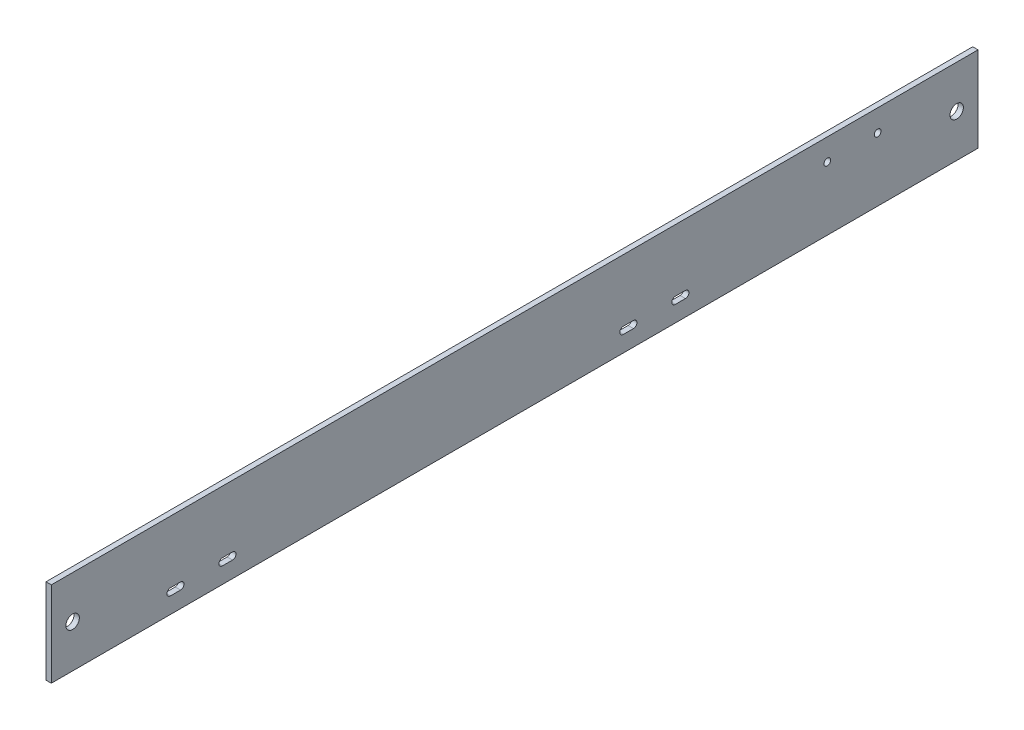
SolidWorks part; units mm, degrees
ref_plane "Front Plane" through (0, 0, 0) normal (0, 0, 1) x (1, 0, 0)
ref_plane "Top Plane" through (0, 0, 0) normal (0, 1, 0) x (1, 0, 0)
ref_plane "Right Plane" through (0, 0, 0) normal (1, 0, 0) x (0, 0, -1)
sketch "Sketch1" plane through (0, 0, 0) normal (1, 0, 0) x (0, 0, -1)
  line L0 (71.025, 11.7) -> (77.025, 11.7) construction
  line L1 (0, 0) -> (552.45, 0)
  line L2 (0, 0) -> (0, 50.8)
  line L3 (0, 50.8) -> (552.45, 50.8)
  line L4 (552.45, 0) -> (552.45, 50.8)
  line L5 (71.025, 13.8) -> (77.025, 13.8)
  line L6 (71.025, 9.6) -> (77.025, 9.6)
  line L7 (102.025, 11.7) -> (108.025, 11.7) construction
  line L8 (102.025, 13.8) -> (108.025, 13.8)
  line L9 (102.025, 9.6) -> (108.025, 9.6)
  line L10 (341.025, 11.7) -> (347.025, 11.7) construction
  line L11 (341.025, 13.8) -> (347.025, 13.8)
  line L12 (341.025, 9.6) -> (347.025, 9.6)
  line L13 (372.025, 11.7) -> (378.025, 11.7) construction
  line L14 (372.025, 13.8) -> (378.025, 13.8)
  line L15 (372.025, 9.6) -> (378.025, 9.6)
  circle A0 centre (12.7, 25.4) radius 4
  circle A1 centre (539.75, 25.4) radius 4
  arc A2 (71.025, 13.8) -> (71.025, 9.6) centre (71.025, 11.7) ccw
  arc A3 (77.025, 9.6) -> (77.025, 13.8) centre (77.025, 11.7) ccw
  arc A4 (102.025, 13.8) -> (102.025, 9.6) centre (102.025, 11.7) ccw
  arc A5 (108.025, 9.6) -> (108.025, 13.8) centre (108.025, 11.7) ccw
  arc A6 (341.025, 13.8) -> (341.025, 9.6) centre (341.025, 11.7) ccw
  arc A7 (347.025, 9.6) -> (347.025, 13.8) centre (347.025, 11.7) ccw
  arc A8 (372.025, 13.8) -> (372.025, 9.6) centre (372.025, 11.7) ccw
  arc A9 (378.025, 9.6) -> (378.025, 13.8) centre (378.025, 11.7) ccw
  circle A10 centre (462.625, 37.8) radius 2
  circle A11 centre (492.625, 37.8) radius 2
  point P11 (74.025, 11.7)
  point P16 (105.025, 11.7)
  point P23 (344.025, 11.7)
  point P30 (375.025, 11.7)
  dimension "D3" = 8
  dimension "D8" = 4.2
  dimension "D20" = 4
  dimension "D1" = 50.8
  dimension "D2" = 552.45
  dimension "D4" = 25.4
  dimension "D5" = 12.7
  dimension "D6" = 12.7
  dimension "D7" = 6
  dimension "D9" = 31
  dimension "D10" = 31
  dimension "D11" = 270
  dimension "D13" = 39.1
  dimension "D12" = 74.025
  dimension "D14" = 539.75
  dimension "D15" = 344.025
  dimension "D16" = 105.025
  dimension "D17" = 375.025
  dimension "D18" = 30
  dimension "D19" = 59.825
  dimension "D21" = 13
  dimension "D22" = 462.625
extrude "Boss-Extrude2" add sketch "Sketch1" along normal blind 3.175
equation "\"RailThickness\"= .125in'Spec"
equation "\"VSWidth\"= 1.25in'Spec"
equation "\"SideRailLength\"= 21.75in"
equation "\"LowerRailHeight\"= 2.0in"
equation "\"StepperHolePadSize\"= \"StepperHoleDiameter\""
equation "\"DistanceFromFrontSideToFirstLeftStepperHoleMountYSValue\"= 74.025mm"
equation "\"DistanceBetweenFrontToBackStepperHoles\"= \"BedLength\" - \"BuildPlateStandoffHolesDistanceFromFrontOrBackSide\" * 2'Equals 270"
equation "\"BedLength\"= \"BuildPlateLength\""
equation "\"D1@Sketch1\"=\"LowerRailHeight\""
equation "\"D2@Sketch1\"=\"SideRailLength\""
equation "\"FrameFastenerHoleDiameter\"= 8mm"
equation "\"D3@Sketch1\"=\"FrameFastenerHoleDiameter\""
equation "\"D4@Sketch1\"=\"LowerRailHeight\"/2"
equation "\"D5@Sketch1\"=\"FrameFastenerHoleOffsetFromEdge\""
equation "\"D6@Sketch1\"=\"FrameFastenerHoleOffsetFromEdge\""
equation "\"D8@Sketch1\"=\"StepperMountSlotDiameterOnRails\""
equation "\"D11@Sketch1\"=\"DistanceBetweenFrontToBackStepperHoles\""
equation "\"D1@Boss-Extrude2\"=\"RailThickness\""
equation "\"FrameFastenerHoleOffsetFromEdge\"= \"VSWidth\" / 2 - \"GapBetweenVerticalSupportsAndRails\" / 2"
equation "\"StepperMountSlotDiameterOnRails\"= 4.2mm"
equation "\"StepperMountSlotWidth\"= 6mm"
equation "\"D7@Sketch1\"=\"StepperMountSlotWidth\""
equation "\"Nema17StepperMountSlotDistance\"= 31mm'Spec"
equation "\"D9@Sketch1\"=\"Nema17StepperMountSlotDistance\""
equation "\"D10@Sketch1\"=\"Nema17StepperMountSlotDistance\""
equation "\"BuildPlateLength\"= 352mm'Spec"
equation "\"BuildPlateStandoffHolesDistanceFromFrontOrBackSide\"= 41mm"
equation "\"D13@Sketch1\"=\"OffsetToGive10mmZAxisMovement\""
equation "\"D12@Sketch1\"=\"DistanceFromFrontSideToFirstLeftStepperHoleMountYSValue\""
equation "\"OffsetToGive10mmZAxisMovement\"= \"LowerRailHeight\" / 2 + 13.7mm'Allow Stepper 10mm Vertical movement"
equation "\"GapBetweenVerticalSupportsAndRails\"= \"RailThickness\" * 2"
equation "\"AngleBracketSmallHoleDiameter\"= 4mm"
equation "\"AngleBracketSlotDistanceBetweenHoles\"= 30mm"
equation "\"AngleBracketSlotDistanceFromTop\"= 13mm"
equation "\"AngleBracketSlotDistanceFromCorner\"= \"AngleBracketSlotDistanceFromBack\" - \"GapBetweenVerticalSupportsAndRails\" / 2'Equals 61.825"
equation "\"AngleBracketSlotDistanceFromBack\"= 65mm"
equation "\"D18@Sketch1\"=\"AngleBracketSlotDistanceBetweenHoles\""
equation "\"D19@Sketch1\"=\"AngleBracketSlotDistanceFromCorner\" - 2mm"
equation "\"D20@Sketch1\"=\"AngleBracketSmallHoleDiameter\""
equation "\"D21@Sketch1\"=\"AngleBracketSlotDistanceFromTop\""
